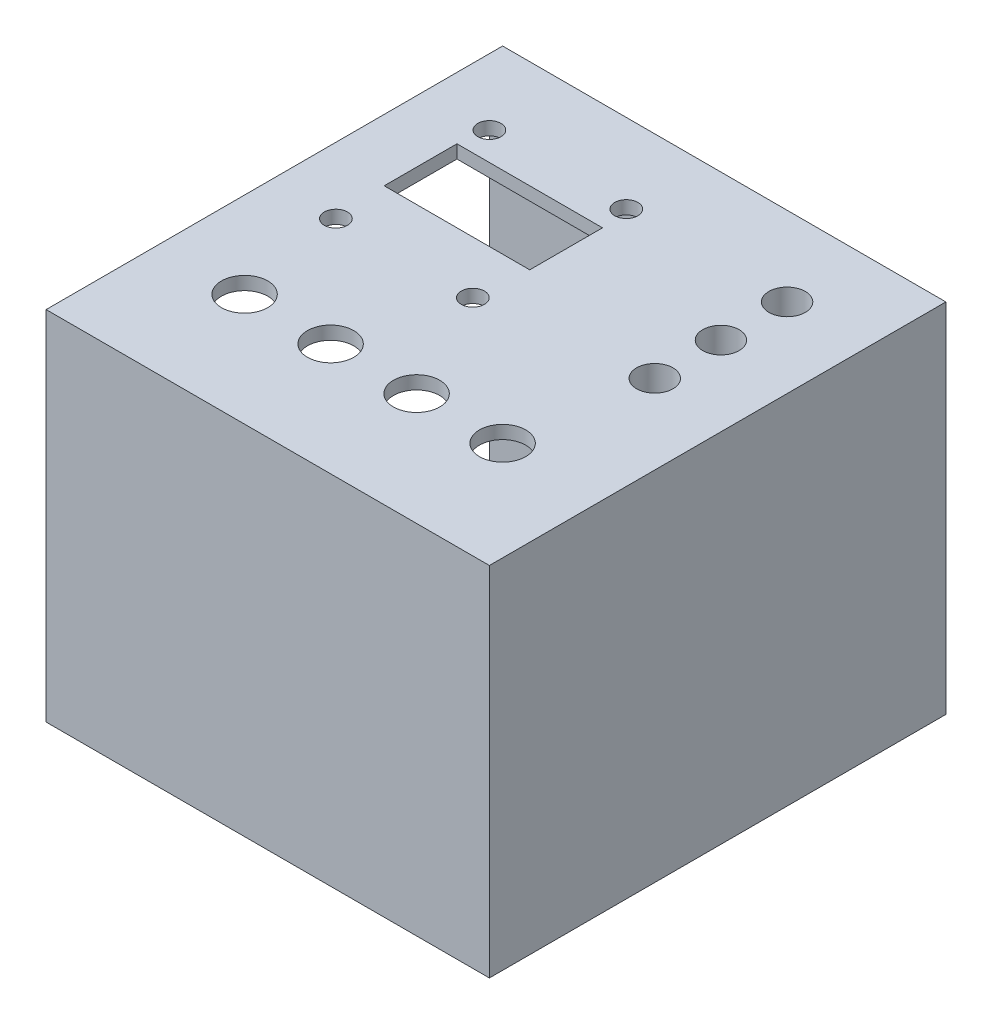
SolidWorks part; units mm, degrees
ref_plane "Front Plane" through (0, 0, 0) normal (0, 0, 1) x (1, 0, 0)
ref_plane "Top Plane" through (0, 0, 0) normal (0, 1, 0) x (1, 0, 0)
ref_plane "Right Plane" through (0, 0, 0) normal (1, 0, 0) x (0, 0, -1)
sketch "Sketch9" plane through (0, 0, 0) normal (0, 1, 0) x (1, 0, 0)
  line L1 (-32.5, 32.5) -> (32.5, 32.5)
  line L2 (-32.5, 32.5) -> (-32.5, -32.5)
  line L3 (-32.5, -32.5) -> (32.5, -32.5)
  line L4 (32.5, 32.5) -> (32.5, -32.5)
  line L5 (-32.5, 32.5) -> (32.5, -32.5) construction
  line L6 (-32.5, -32.5) -> (32.5, 32.5) construction
  point P0 (0, 0)
  dimension "D1" = 65
  dimension "D2" = 65
extrude "Boss-Extrude1" add sketch "Sketch9" against normal blind 52
shell "Shell3" thickness 2 removed face at (0, -52, 0) removed face at (-32.5, -26, 0) outward yes
sketch "Sketch11" plane through (0, 2, 0) normal (0, 1, 0) x (1, 0, 0)
  line L0 (-32.5, 34.5) -> (-32.5, -34.5) construction
  line L1 (34.5, 34.5) -> (-32.5, 34.5) construction
  line L2 (-25.8, 24.55) -> (1.5, 24.55) construction
  line L4 (-25.8, 24.55) -> (-25.8, -2.75) construction
  line L5 (-25.8, -2.75) -> (1.5, -2.75) construction
  line L6 (34.5, -34.5) -> (34.5, 34.5) construction
  line L7 (1, -34.5) -> (1, 34.5) construction
  line L8 (-32.5, -34.5) -> (34.5, -34.5) construction
  line L9 (34.5, 34.5) -> (-32.5, 34.5) construction
  line L17 (-12.15, 18.25) -> (-12.15, 7.25) construction
  line L18 (-23.15, 7.25) -> (-1.15, 7.25)
  line L19 (-23.15, 7.25) -> (-23.15, 18.25)
  line L20 (-23.15, 18.25) -> (-1.15, 18.25)
  line L21 (-1.15, 7.25) -> (-1.15, 18.25)
  line L22 (-1.15, 12.75) -> (-23.15, 12.75) construction
  line L23 (1.5, 24.55) -> (1.5, -2.75) construction
  line L24 (-23.02, 7.32) -> (-1.28, 7.32) construction
  line L25 (-23.02, 7.32) -> (-23.02, 18.18) construction
  line L26 (-23.02, 18.18) -> (-1.28, 18.18) construction
  line L27 (-1.28, 7.32) -> (-1.28, 18.18) construction
  line L28 (-23.02, 7.32) -> (-1.28, 18.18) construction
  line L29 (-23.02, 18.18) -> (-1.28, 7.32) construction
  line L30 (-32.5, 32.5) -> (32.5, 32.5) construction
  line L31 (-32.5, 32.5) -> (-32.5, -32.5) construction
  line L32 (-32.5, -32.5) -> (32.5, -32.5) construction
  line L33 (32.5, 32.5) -> (32.5, -32.5) construction
  line L36 (-32.5, 32.5) -> (32.5, -32.5) construction
  circle A0 centre (-22.5, 22.5) radius 1.75
  circle A1 centre (-22.5, -0.7) radius 1.75
  circle A2 centre (-1.8, -0.7) radius 1.75
  circle A3 centre (-1.8, 22.5) radius 1.75
  point P12 (0, 0)
  point P13 (1, 0)
  point P14 (-12.15, 12.75)
  point P27 (-12.15, 12.75)
  point P44 (-22.5, 22.5)
  point P46 (-22.5161, 22.5161)
  dimension "D10" = 3.5
  dimension "D11" = 3.5
  dimension "D1" = 22
  dimension "D2" = 11
  dimension "D3" = 10.86
  dimension "D4" = 21.74
  dimension "D5" = 27.3
  dimension "D6" = 27.3
  dimension "D7" = 6.37
  dimension "D8" = 2.05
  dimension "D9" = 3.3
  dimension "D12" = 23.2
  dimension "D13" = 3.3
  dimension "D14" = 2
  dimension "D15" = 2
  dimension "D16" = 10
  dimension "D17" = 0
  dimension "D18" = 2
  dimension "D19" = 10
extrude "Cut-Extrude1" cut sketch "Sketch11" against normal up to surface (2 mm away) up to face at (0, 0, 0)
sketch "Sketch12" plane through (0, 2, 0) normal (0, 1, 0) x (1, 0, 0)
  line L0 (-32.5, -17.5) -> (34.5, -17.5) construction
  line L1 (-32.5, 34.5) -> (-32.5, -34.5) construction
  line L2 (34.5, -34.5) -> (34.5, 34.5) construction
  line L3 (-32.5, -34.5) -> (34.5, -34.5) construction
  circle A0 centre (-19.5, -17.5) radius 3.5
  circle A1 centre (-6.5, -17.5) radius 3.5
  circle A2 centre (6.5, -17.5) radius 3.5
  circle A3 centre (19.5, -17.5) radius 3.5
  point P16 (-3.9721, -17.5)
  point P17 (8.1117, -17.5)
  point P18 (21.7485, -17.5)
  dimension "D2" = 7
  dimension "D7" = 7
  dimension "D8" = 7
  dimension "D9" = 7
  dimension "D1" = 17
  dimension "D3" = 15
  dimension "D4" = 13
  dimension "D5" = 13
  dimension "D6" = 13
extrude "Cut-Extrude3" cut sketch "Sketch12" against normal up to surface (2 mm away) up to face at (-1.8, 0, -20.75)
sketch "Sketch13" plane through (0, 2, 0) normal (0, 1, 0) x (1, 0, 0)
  line L0 (34.5, -34.5) -> (34.5, 34.5) construction
  line L2 (34.5, 34.5) -> (-32.5, 34.5) construction
  circle A4 centre (22.5, 22.5) radius 2.75
  circle A7 centre (22.5, 12.5) radius 2.75
  circle A10 centre (22.5, 2.5) radius 2.75
  dimension "D2" = 12
  dimension "D3" = 12
  dimension "D6" = 3
extrude "Cut-Extrude5" cut sketch "Sketch13" against normal up to surface (2 mm away) up to face at (-19.5, 0, 21)
sketch "Sketch14" plane through (0, 0, 0) normal (0, -1, 0) x (1, 0, 0)
  circle A0 centre (22.5, -22.5) radius 2.75
  circle A1 centre (22.5, -22.5) radius 3.75
  circle A2 centre (22.5, -12.5) radius 2.75
  circle A3 centre (22.5, -12.5) radius 3.75
  circle A4 centre (22.5, -2.5) radius 2.75
  circle A5 centre (22.5, -2.5) radius 3.75
  dimension "D1" = 1
  dimension "D2" = 3
extrude "Boss-Extrude2" add sketch "Sketch14" along normal blind 7.7
